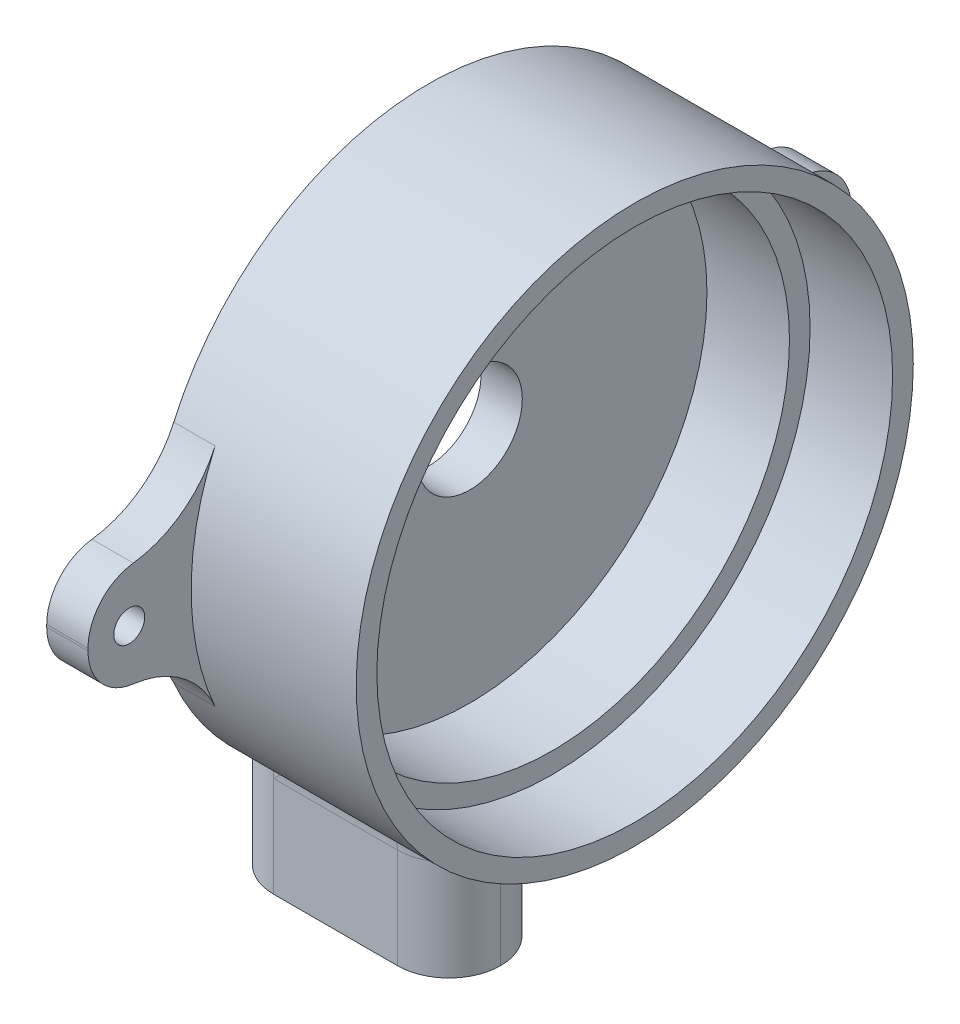
SolidWorks part; units mm, degrees
ref_plane "前视基准面" through (0, 0, 0) normal (0, 0, 1) x (1, 0, 0)
ref_plane "上视基准面" through (0, 0, 0) normal (0, 1, 0) x (1, 0, 0)
ref_plane "右视基准面" through (0, 0, 0) normal (1, 0, 0) x (0, 0, -1)
other "Configuration Table"
sketch "草图1" plane through (0, 0, 0) normal (1, 0, 0) x (0, 0, -1)
  circle A0 centre (0, 0) radius 27
  dimension "D1" = 54
extrude "凸台-拉伸1" add sketch "草图1" along normal blind 20
sketch "草图10" plane through (0, 0, 0) normal (-1, 0, 0) x (0, 0, 1)
  line L0 (0, 0) -> (13.6346, 0) construction
  line L1 (0, 0) -> (0, 7.8949) construction
  line L2 (0, 5) -> (37, 5)
  line L7 (-37, 5) -> (0, 5)
  line L8 (-37, 5) -> (-37, -5)
  line L9 (-37, -5) -> (0, -5)
  line L11 (37, 5) -> (37, -5)
  line L12 (37, -5) -> (0, -5)
  dimension "D1" = 37
  dimension "D2" = 10
  dimension "D3" = 5
  dimension "D4" = 37
extrude "凸台-拉伸2" add sketch "草图10" against normal blind 4
sketch "草图2" plane through (20, 0, 0) normal (1, 0, 0) x (0, 0, -1)
  circle A0 centre (0, 0) radius 25
  dimension "D1" = 50
extrude "切除-拉伸1" cut sketch "草图2" against normal blind 8
sketch "草图3" plane through (12, 0, 0) normal (1, 0, 0) x (0, 0, -1)
  circle A0 centre (0, 0) radius 23
  dimension "D1" = 46
extrude "切除-拉伸2" cut sketch "草图3" against normal blind 8
sketch "草图8" plane through (4, 0, 0) normal (1, 0, 0) x (0, 0, -1)
  circle A0 centre (0, 0) radius 5.1
  dimension "D1" = 10.2
extrude "切除-拉伸5" cut sketch "草图8" against normal up to next
sketch "草图11" plane through (4, 0, 0) normal (1, 0, 0) x (0, 0, -1)
  line L0 (-37, 0) -> (37, 0) construction
  line L1 (-37, -5) -> (-37, 5) construction
  line L2 (37, 5) -> (37, -5) construction
  circle A0 centre (-33, 0) radius 1.5
  circle A1 centre (33, 0) radius 1.5
  dimension "D1" = 3
  dimension "D2" = 3
  dimension "D3" = 4
  dimension "D4" = 4
extrude "切除-拉伸6" cut sketch "草图11" against normal up to next
fillet "圆角1" radius 10 4 edges at (2, 5, -26.533) (2, -5, -26.533) (2, -5, 26.533) (2, 5, 26.533)
fillet "圆角2" radius 5 4 edges at (2, 5, 37) (2, -5, 37) (2, -5, -37) (2, 5, -37)
sketch "草图12" plane through (0, 0, 0) normal (-1, 0, 0) x (0, 0, 1)
  line L0 (0, 27) -> (0, -27) construction
  line L6 (-5, -26.533) -> (5, -26.533)
  line L7 (-5, -26.533) -> (-5, -21.533)
  line L8 (-5, -21.533) -> (5, -21.533)
  line L9 (5, -26.533) -> (5, -21.533)
  arc A0 (24.6817, 10.9459) -> (-24.6817, 10.9459) centre (0, 0) ccw construction
  arc A1 (-24.6817, -10.9459) -> (24.6817, -10.9459) centre (0, 0) ccw construction
  point P12 (6.5728, -26.1878)
  dimension "D1" = 10
  dimension "D2" = 5
extrude "凸台-拉伸3" add sketch "草图12" along normal blind 15
sketch "草图13" plane through (0, -26.533, 0) normal (0, -1, 0) x (1, 0, 0)
  line L1 (-15, 5) -> (7, 5)
  line L2 (-15, 5) -> (-15, -5)
  line L3 (-15, -5) -> (7, -5)
  line L4 (7, 5) -> (7, -5)
  point P5 (-15, -5)
  dimension "D1" = 22
extrude "凸台-拉伸4" add sketch "草图13" along normal blind 17
fillet "圆角3" radius 10 4 edges at (3.5, -26.533, -5) (3.5, -26.533, 5) (0, -24.033, 5) (0, -24.033, -5)
fillet "圆角4" radius 13 1 edges at (0, -21.533, 0) first distance on face at (0, 0, -5.1)
sketch "草图14" plane through (0, -43.533, 0) normal (0, -1, 0) x (-1, 0, 0)
  line L0 (15, 0) -> (-7, 0) construction
  line L1 (15, -5) -> (15, 5) construction
  line L2 (-7, 5) -> (-7, -5) construction
  circle A0 centre (9, 0) radius 3
  dimension "D1" = 6
  dimension "D2" = 6
extrude "切除-拉伸7" cut sketch "草图14" against normal up to next
fillet "圆角5" radius 5 6 edges at (7, -28.3706, -6.6173) (7, -28.3706, 6.6173) (7, -38.678, -5) (7, -38.678, 5) (-15, -32.533, 5) (-15, -32.533, -5)
